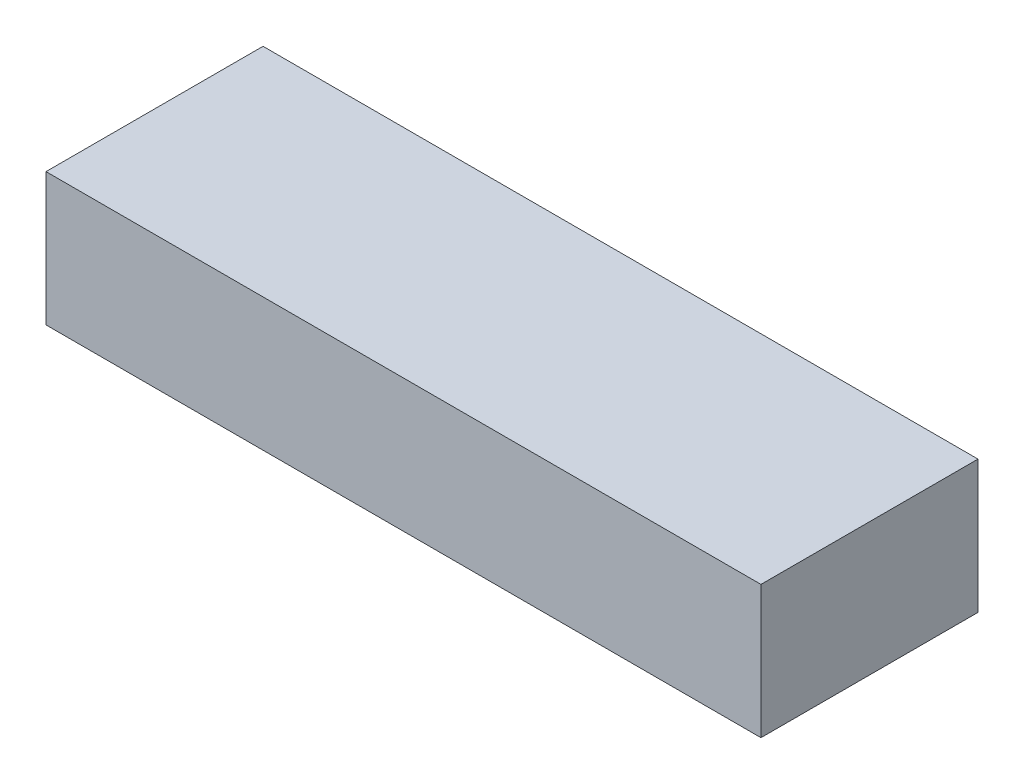
SolidWorks part; units mm, degrees
ref_plane "前视基准面" through (0, 0, 0) normal (0, 0, 1) x (1, 0, 0)
ref_plane "上视基准面" through (0, 0, 0) normal (0, 1, 0) x (1, 0, 0)
ref_plane "右视基准面" through (0, 0, 0) normal (1, 0, 0) x (0, 0, -1)
other "Configuration Table"
sketch "草图1" plane through (0, 0, 0) normal (0, 1, 0) x (1, 0, 0)
  line L1 (-70, -21.25) -> (70, -21.25)
  line L2 (-70, -21.25) -> (-70, 21.25)
  line L3 (-70, 21.25) -> (70, 21.25)
  line L4 (70, -21.25) -> (70, 21.25)
  line L5 (-70, -21.25) -> (70, 21.25) construction
  line L6 (-70, 21.25) -> (70, -21.25) construction
  point P0 (0, 0)
  dimension "D1" = 140
  dimension "D2" = 42.5
extrude "凸台-拉伸1" add sketch "草图1" along normal blind 13 and the other way blind 13
